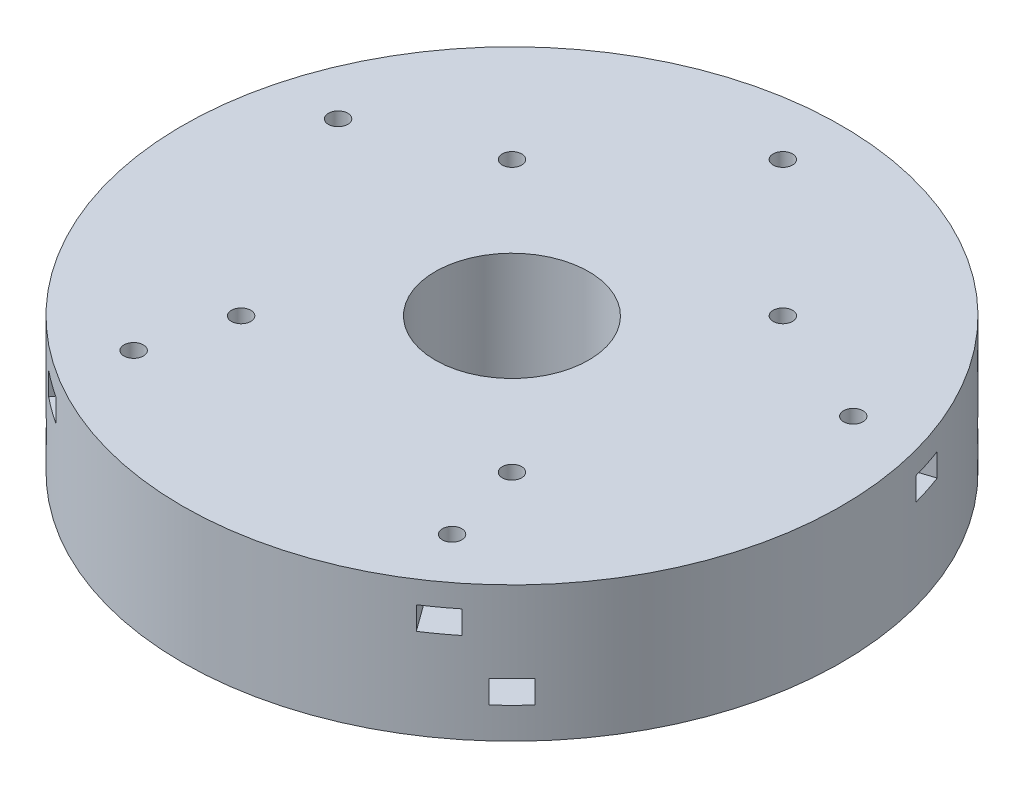
SolidWorks part; units mm, degrees
ref_plane "Front Plane" through (0, 0, 0) normal (0, 0, 1) x (1, 0, 0)
ref_plane "Top Plane" through (0, 0, 0) normal (0, 1, 0) x (1, 0, 0)
ref_plane "Right Plane" through (0, 0, 0) normal (1, 0, 0) x (0, 0, -1)
sketch "Sketch1" plane through (0, 0, 0) normal (0, 1, 0) x (1, 0, 0)
  line L0 (0, 30) -> (0, -30) construction
  line L1 (-30, -30) -> (30, -30) construction
  line L2 (-30, -30) -> (-30, 30) construction
  line L3 (-30, 30) -> (30, 30) construction
  line L4 (30, -30) -> (30, 30) construction
  line L5 (-30, -30) -> (30, 30) construction
  line L6 (-30, 30) -> (30, -30) construction
  line L7 (-30, 0) -> (30, 0) construction
  circle A0 centre (0, 0) radius 73
  circle A1 centre (30, 30) radius 2.15
  circle A3 centre (-30, 30) radius 2.15
  circle A4 centre (30, -30) radius 2.15
  circle A5 centre (-30, -30) radius 2.15
  circle A6 centre (0, 60) radius 2.15
  circle A7 centre (57.0634, 18.541) radius 2.15
  circle A8 centre (35.2671, -48.541) radius 2.15
  circle A9 centre (-35.2671, -48.541) radius 2.15
  circle A10 centre (-57.0634, 18.541) radius 2.15
  point P27 (0, 0)
  dimension "D1" = 146
  dimension "D4" = 4.3
  dimension "D5" = 60
  dimension "4.3" = 4.3
  dimension "D2" = 60
  dimension "D3" = 60
  dimension "D6" = 5
extrude "Boss-Extrude1" add sketch "Sketch1" along normal blind 30
ref_plane "Plane1" through (0, 12, 0) normal (0, 1, 0) x (1, 0, 0)
sketch "Sketch2" plane through (0, 12, 0) normal (0, 1, 0) x (1, 0, 0)
  line L0 (-30, 30) -> (0, 0) construction
  line L1 (-27.0402, 27.0402) -> (-25.9568, 31.0834)
  line L2 (-25.9568, 31.0834) -> (-28.9166, 34.0432)
  line L5 (-34.0432, 28.9166) -> (-31.0834, 25.9568)
  line L6 (-31.0834, 25.9568) -> (-27.0402, 27.0402)
  line L7 (-34.0432, 28.9166) -> (-54.1184, 48.9919)
  line L8 (-28.9166, 34.0432) -> (-48.9919, 54.1184)
  line L9 (28.9166, 34.0432) -> (25.9568, 31.0834)
  line L10 (-28.9166, 34.0432) -> (-30.9382, 33.5015) [skipped]
  line L11 (-33.5015, 30.9382) -> (-34.0432, 28.9166) [skipped]
  line L12 (25.9568, 31.0834) -> (27.0402, 27.0402)
  line L13 (27.0402, 27.0402) -> (31.0834, 25.9568)
  line L14 (31.0834, 25.9568) -> (34.0432, 28.9166)
  line L15 (34.0432, 28.9166) -> (54.1184, 48.9919)
  line L16 (28.9166, 34.0432) -> (48.9919, 54.1184)
  line L17 (34.0432, -28.9166) -> (31.0834, -25.9568)
  line L18 (31.0834, -25.9568) -> (27.0402, -27.0402)
  line L19 (27.0402, -27.0402) -> (25.9568, -31.0834)
  line L20 (25.9568, -31.0834) -> (28.9166, -34.0432)
  line L21 (28.9166, -34.0432) -> (48.9919, -54.1184)
  line L22 (34.0432, -28.9166) -> (54.1184, -48.9919)
  line L23 (-28.9166, -34.0432) -> (-25.9568, -31.0834)
  line L24 (-25.9568, -31.0834) -> (-27.0402, -27.0402)
  line L25 (-27.0402, -27.0402) -> (-31.0834, -25.9568)
  line L26 (-31.0834, -25.9568) -> (-34.0432, -28.9166)
  line L27 (-34.0432, -28.9166) -> (-54.1184, -48.9919)
  line L28 (-28.9166, -34.0432) -> (-48.9919, -54.1184)
  arc A0 (-32.5633, 27.4367) -> (-27.4367, 32.5633) centre (-30, 30) ccw construction
  circle A1 centre (0, 0) radius 73 construction
  arc A2 (-48.9919, 54.1184) -> (-54.1184, 48.9919) centre (0, 0) ccw
  arc A3 (54.1184, 48.9919) -> (48.9919, 54.1184) centre (0, 0) ccw
  arc A4 (48.9919, -54.1184) -> (54.1184, -48.9919) centre (0, 0) ccw
  arc A5 (-54.1184, -48.9919) -> (-48.9919, -54.1184) centre (0, 0) ccw
  point P42 (0, 0)
  dimension "D1" = 0
  dimension "D2" = 7.25
  dimension "D3" = 0
  dimension "D4" = 4
extrude "Cut-Extrude1" cut sketch "Sketch2" against normal blind 5.1
ref_plane "Plane2" through (0, 20, 0) normal (0, 1, 0) x (1, 0, 0)
sketch "Sketch4" plane through (0, 20, 0) normal (0, 1, 0) x (1, 0, 0)
  line L0 (-3.625, 62.0929) -> (-3.625, 72.9099)
  line L1 (0, 55.8142) -> (3.625, 57.9071)
  line L2 (3.625, 57.9071) -> (3.625, 62.0929)
  line L5 (-3.625, 62.0929) -> (-3.625, 57.9071)
  line L6 (-3.625, 57.9071) -> (0, 55.8142)
  line L7 (3.625, 62.0929) -> (3.625, 72.9099)
  line L8 (56.1931, 14.4467) -> (60.174, 15.7402)
  line L9 (-1.8125, 63.1393) -> (-3.625, 62.0929) [skipped]
  line L10 (3.625, 62.0929) -> (1.8125, 63.1393) [skipped]
  line L11 (53.0825, 17.2475) -> (56.1931, 14.4467)
  line L12 (53.9527, 21.3419) -> (53.0825, 17.2475)
  line L13 (57.9337, 22.6353) -> (53.9527, 21.3419)
  line L14 (57.9337, 22.6353) -> (68.2213, 25.978)
  line L15 (60.174, 15.7402) -> (70.4617, 19.0828)
  line L16 (31.1043, -48.9786) -> (33.5646, -52.3649)
  line L17 (32.8068, -45.1546) -> (31.1043, -48.9786)
  line L18 (36.9696, -44.7171) -> (32.8068, -45.1546)
  line L19 (39.43, -48.1035) -> (36.9696, -44.7171)
  line L20 (39.43, -48.1035) -> (45.7881, -56.8547)
  line L21 (33.5646, -52.3649) -> (39.9227, -61.1161)
  line L22 (-36.9696, -44.7171) -> (-39.43, -48.1035)
  line L23 (-32.8068, -45.1546) -> (-36.9696, -44.7171)
  line L24 (-31.1043, -48.9786) -> (-32.8068, -45.1546)
  line L25 (-33.5646, -52.3649) -> (-31.1043, -48.9786)
  line L26 (-33.5646, -52.3649) -> (-39.9227, -61.1161)
  line L27 (-39.43, -48.1035) -> (-45.7881, -56.8547)
  line L28 (-53.9527, 21.3419) -> (-57.9337, 22.6353)
  line L29 (-53.0825, 17.2475) -> (-53.9527, 21.3419)
  line L30 (-56.1931, 14.4467) -> (-53.0825, 17.2475)
  line L31 (-60.174, 15.7402) -> (-56.1931, 14.4467)
  line L32 (-60.174, 15.7402) -> (-70.4617, 19.0828)
  line L33 (-57.9337, 22.6353) -> (-68.2213, 25.978)
  circle A0 centre (0, 60) radius 3.625 construction
  circle A1 centre (0, 0) radius 73 construction
  arc A2 (3.625, 72.9099) -> (-3.625, 72.9099) centre (0, 0) ccw
  arc A3 (70.4617, 19.0828) -> (68.2213, 25.978) centre (0, 0) ccw
  arc A4 (39.9227, -61.1161) -> (45.7881, -56.8547) centre (0, 0) ccw
  arc A5 (-45.7881, -56.8547) -> (-39.9227, -61.1161) centre (0, 0) ccw
  arc A6 (-68.2213, 25.978) -> (-70.4617, 19.0828) centre (0, 0) ccw
  point P46 (0, 0)
  dimension "D1" = 7.25
  dimension "D2" = 5
extrude "Cut-Extrude2" cut sketch "Sketch4" along normal blind 5.1
sketch "Sketch5" plane through (0, 30, 0) normal (0, 1, 0) x (1, 0, 0)
  circle A0 centre (0, 0) radius 17
  dimension "D1" = 34
extrude "Cut-Extrude3" cut sketch "Sketch5" against normal through all
